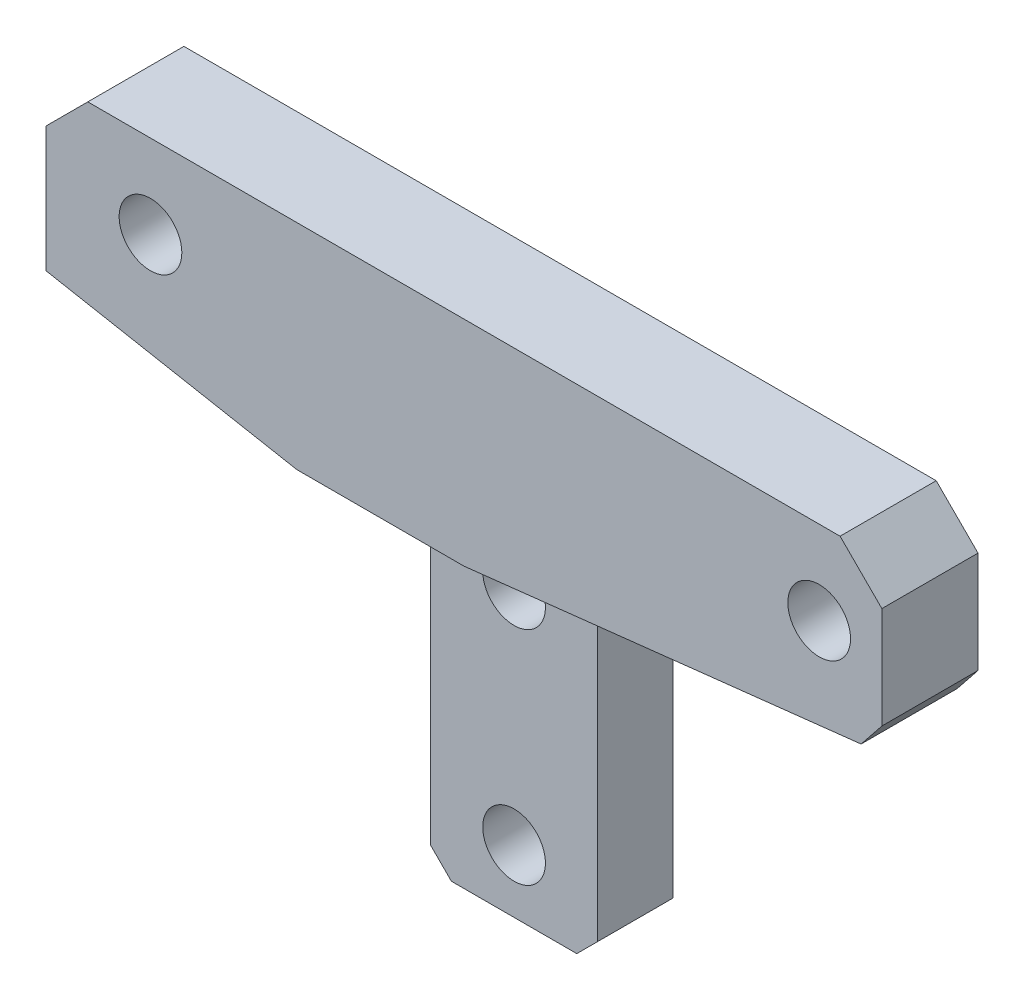
SolidWorks part; units mm, degrees
ref_plane "前视基准面" through (0, 0, 0) normal (0, 0, 1) x (1, 0, 0)
ref_plane "上视基准面" through (0, 0, 0) normal (0, 1, 0) x (1, 0, 0)
ref_plane "右视基准面" through (0, 0, 0) normal (1, 0, 0) x (0, 0, -1)
other "Configuration Table"
sketch "草图1" plane through (0, 0, 0) normal (0, 0, 1) x (1, 0, 0)
  line L1 (-10, 2) -> (10, 2)
  line L2 (-10, 2) -> (-10, -2)
  line L4 (10, 2) -> (10, -2)
  line L5 (-10, 2) -> (10, -2) construction
  line L6 (-10, -2) -> (10, 2) construction
  line L8 (-4, -3.12) -> (-4, -13)
  line L9 (-4, -13) -> (0, -13)
  line L10 (0, -3.12) -> (0, -13)
  line L11 (-10, -2) -> (-4, -3.12)
  line L12 (0, -3.12) -> (10, -2)
  circle A0 centre (-7.5, 0) radius 0.75
  circle A1 centre (8.5, 0) radius 0.75
  circle A2 centre (-2, -11.5) radius 0.75
  circle A3 centre (-2, -6.2) radius 0.75
  point P0 (0, 0)
  dimension "D5" = 1.12
  dimension "D7" = 9.88
  dimension "D12" = 1.12
  dimension "D4" = 1.5
  dimension "D1" = 20
  dimension "D2" = 4
  dimension "D3" = 4
  dimension "D6" = 2.5
  dimension "D8" = 1.5
  dimension "D9" = 10
  dimension "D10" = 2
  dimension "D11" = 2
  dimension "D14" = 2
  dimension "D15" = 2
  dimension "D16" = 1.5
  dimension "D17" = 5.3
extrude "凸台-拉伸2" add sketch "草图1" along normal blind 5.5
sketch "草图3" plane through (0, 0, 5.5) normal (0, 0, -1) x (-1, 0, 0)
  line L0 (0, -3.12) -> (4, -3.12)
  line L8 (-10, 2) -> (-10, -2)
  line L9 (-10, -2) -> (0, -3.12)
  line L10 (0, -3.12) -> (0, -13)
  line L11 (0, -13) -> (4, -13)
  line L12 (4, -13) -> (4, -3.12)
  line L14 (10, -2) -> (10, 2)
  line L15 (10, 2) -> (-10, 2)
  line L18 (0, -3.12) -> (0, -13)
  line L19 (0, -13) -> (4, -13)
  line L20 (4, -13) -> (4, -3.12)
  line L25 (4, -3.12) -> (10, -2)
  circle A0 centre (2, -11.5) radius 0.75 construction
  circle A1 centre (2, -6.2) radius 0.75 construction
  circle A2 centre (2, -11.5) radius 0.75
  circle A3 centre (2, -6.2) radius 0.75
  dimension "D2" = 0
  dimension "D1" = 0
extrude "切除-拉伸2" cut sketch "草图3" along normal blind 3.2
chamfer "倒角1" distance 1 angle 45 1 edges at (-2, -3.12, 2.3)
chamfer "倒角2" distance 1 angle 45 2 edges at (-10, 2, 2.75) (10, 2, 2.75)
chamfer "倒角3" distance 0.5 angle 45 2 edges at (-4, -13, 1.15) (0, -13, 1.15)
sketch "草图4" plane through (0, 0, 0) normal (0, 0, 1) x (1, 0, 0)
  line L6 (-10, -2.5) -> (10, -2.5)
  line L13 (-4, -3.12) -> (0, -3.12)
  line L17 (0, -3.12) -> (10, -2)
  line L18 (10, -2) -> (10, 1)
  line L19 (10, 1) -> (9, 2)
  line L20 (9, 2) -> (-9, 2)
  line L21 (-9, 2) -> (-10, 1)
  line L22 (-10, 1) -> (-10, -2)
  line L23 (-10, -2) -> (-4, -3.12)
  line L30 (10, -2.5) -> (10, 1)
  line L31 (10, 1) -> (9, 2)
  line L32 (9, 2) -> (-9, 2)
  line L33 (-9, 2) -> (-10, 1)
  line L34 (-10, 1) -> (-10, -2.5)
  circle A0 centre (8.5, 0) radius 0.75 construction
  circle A1 centre (-7.5, 0) radius 0.75 construction
  circle A2 centre (8.5, 0) radius 0.75
  circle A3 centre (-7.5, 0) radius 0.75
  dimension "D2" = 4.5
  dimension "D1" = 0
extrude "切除-拉伸3" cut sketch "草图4" along normal blind 3.2
chamfer "倒角4" distance 0.5 angle 45 1 edges at (10, -2, 4.35) first distance on face at (4.4388, -2.6229, 2.9571)
sketch "草图5" plane through (0, 0, 0) normal (0, 0, -1) x (-1, 0, 0)
  line L8 (4, -3.12) -> (7.3214, -2.5)
  line L9 (7.3214, -2.5) -> (-5.5357, -2.5)
  line L10 (-5.5357, -2.5) -> (0, -3.12)
  line L11 (0, -3.12) -> (0, -12.5)
  line L12 (0, -12.5) -> (0.5, -13)
  line L13 (0.5, -13) -> (3.5, -13)
  line L14 (3.5, -13) -> (4, -12.5)
  line L15 (4, -12.5) -> (4, -3.12)
  line L16 (4, -3.12) -> (7.3214, -2.5)
  line L17 (7.3214, -2.5) -> (-5.5357, -2.5)
  line L18 (-5.5357, -2.5) -> (0, -3.12)
  line L19 (0, -3.12) -> (0, -12.5)
  line L20 (0, -12.5) -> (0.5, -13)
  line L21 (0.5, -13) -> (3.5, -13)
  line L22 (3.5, -13) -> (4, -12.5)
  line L23 (4, -12.5) -> (4, -3.12)
  dimension "D1" = 0
extrude "切除-拉伸4" cut sketch "草图5" against normal blind 0.5
